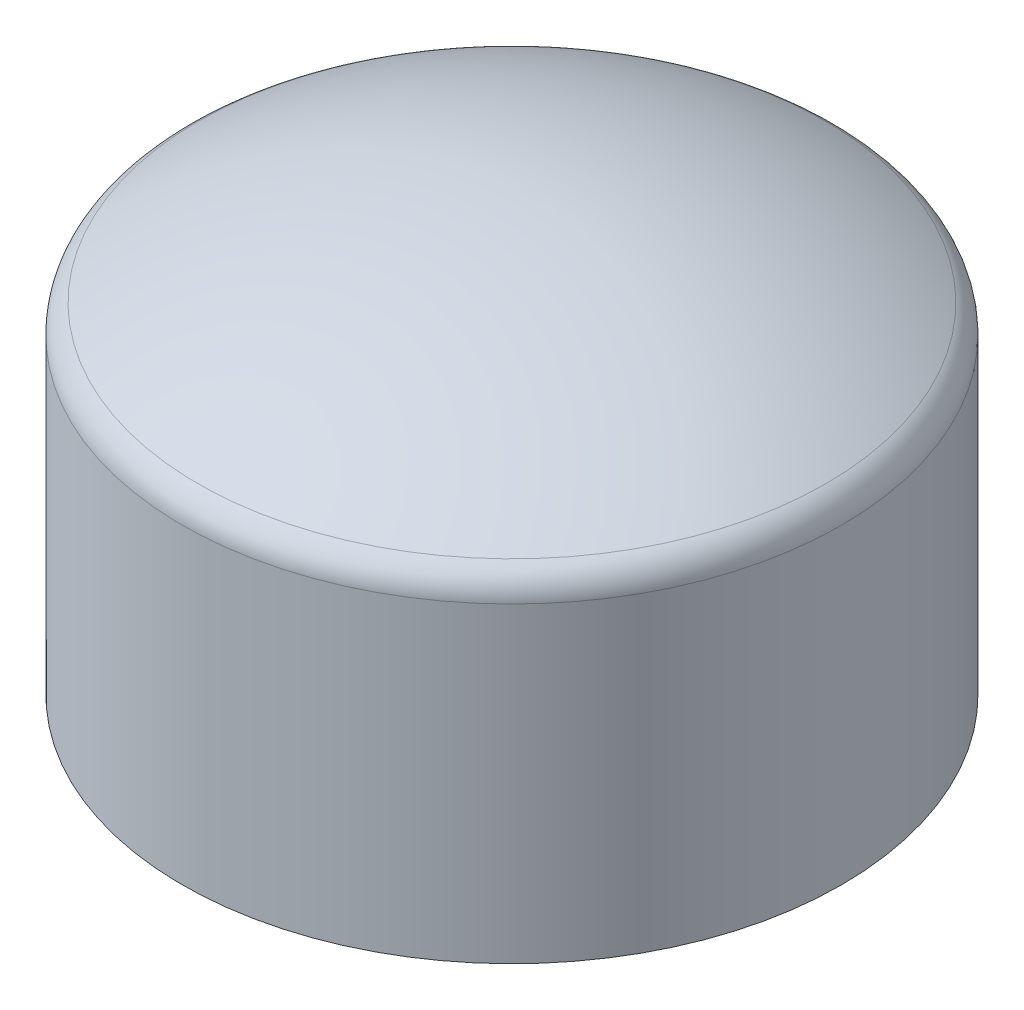
SolidWorks part; units mm, degrees
material "ABS"
ref_plane "Front Plane" through (0, 0, 0) normal (0, 0, 1) x (1, 0, 0)
ref_plane "Top Plane" through (0, 0, 0) normal (0, 1, 0) x (1, 0, 0)
ref_plane "Right Plane" through (0, 0, 0) normal (1, 0, 0) x (0, 0, -1)
sketch "Sketch1" plane through (0, 0, 0) normal (0, 0, 1) x (1, 0, 0)
  line L0 (-8, 0) -> (-10, 0)
  line L1 (-8, 0) -> (8, 0) construction
  line L2 (-8, 0) -> (-8, 9)
  line L3 (-8, 9) -> (0, 9)
  line L5 (-10, 0) -> (-10, 10)
  line L6 (0, 9) -> (0, 13)
  line L7 (0, 13) -> (0.8573, 13) construction
  arc A0 (-10, 10) -> (0, 13) centre (0, -5.1667) cw
  dimension "D3" = 2
  dimension "D1" = 9
  dimension "D2" = 16
  dimension "D4" = 4
  dimension "D5" = 1
revolve "Revolve1" add sketch "Sketch1" angle 360 about L6
fillet "Fillet1" radius 1 1 edges at (10, 10, 0)
sketch "Sketch2" plane through (0, 9, 0) normal (0, -1, 0) x (1, 0, 0)
  line L1 (0, 7.5056) -> (-6.5, 3.7528)
  line L2 (-6.5, 3.7528) -> (-6.5, -3.7528)
  line L3 (-6.5, -3.7528) -> (0, -7.5056)
  line L4 (0, -7.5056) -> (6.5, -3.7528)
  line L5 (6.5, -3.7528) -> (6.5, 3.7528)
  line L6 (6.5, 3.7528) -> (0, 7.5056)
  circle A0 centre (0, 0) radius 6.5 construction
  circle A1 centre (0, 0) radius 8 construction
  circle A2 centre (0, 0) radius 8
  dimension "D1" = 13
extrude "Boss-Extrude1" add sketch "Sketch2" along normal up to surface (9 mm away) up to face at (8, 0, 0)
